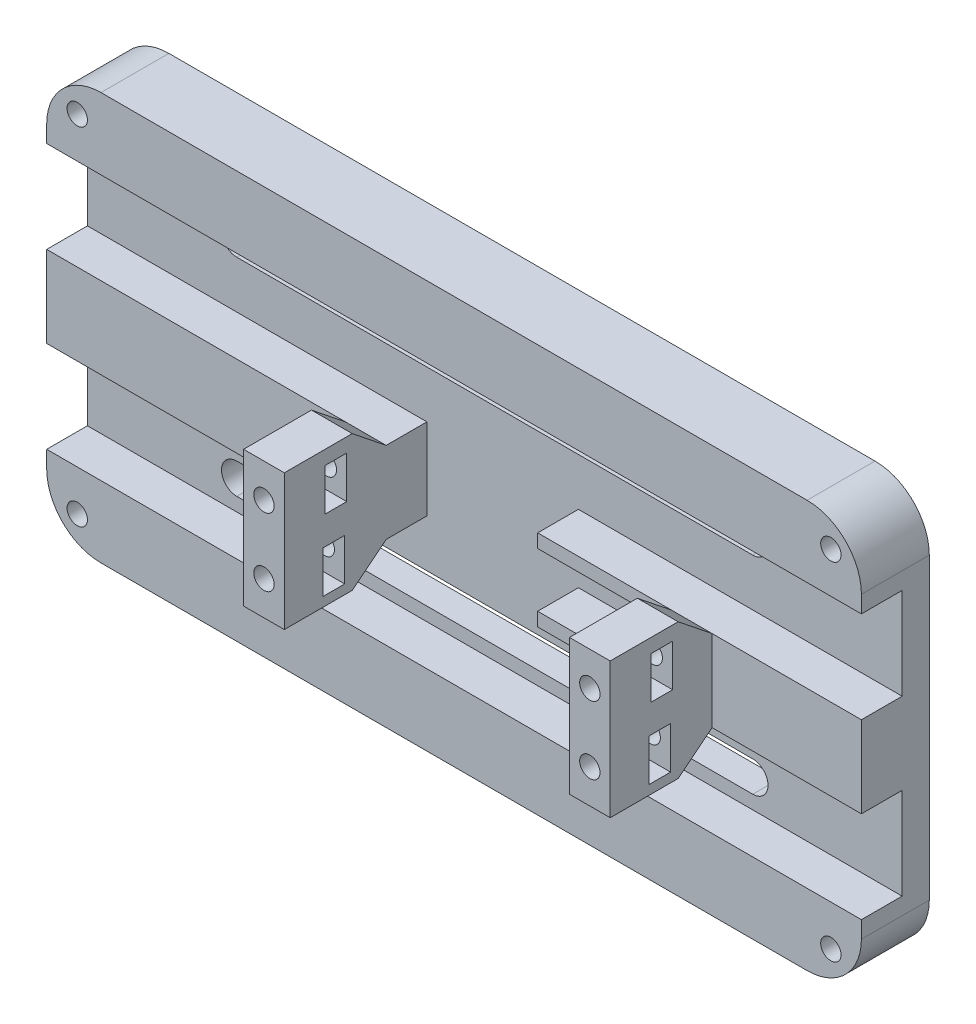
SolidWorks part; units mm, degrees
ref_plane "Front Plane" through (0, 0, 0) normal (0, 0, 1) x (1, 0, 0)
ref_plane "Top Plane" through (0, 0, 0) normal (0, 1, 0) x (1, 0, 0)
ref_plane "Right Plane" through (0, 0, 0) normal (1, 0, 0) x (0, 0, -1)
sketch "Sketch1" plane through (0, 0, 0) normal (0, 0, 1) x (1, 0, 0)
  line L0 (-59.6803, 25.5) -> (60.3197, 25.5)
  line L1 (-59.6803, 36) -> (60.3197, 36)
  line L2 (-59.6803, 36) -> (-59.6803, -24)
  line L3 (-59.6803, -24) -> (60.3197, -24)
  line L4 (60.3197, 36) -> (60.3197, -24)
  line L5 (-59.6803, -13.5) -> (60.3197, -13.5)
  line L6 (-59.6803, 0) -> (-15.6803, 0)
  line L7 (-9.6803, 12) -> (32.3197, 12)
  line L8 (-37.6803, 23.5) -> (38.3197, 23.5)
  line L9 (-37.6803, -11.5) -> (38.3197, -11.5)
  line L10 (-37.6803, 19) -> (38.3197, 19)
  line L11 (-37.6803, -7) -> (38.3197, -7)
  line L17 (38.3197, 12) -> (38.3197, 0)
  line L18 (-9.6803, 0) -> (32.3197, 0)
  line L19 (38.3197, -3.5007) -> (38.3197, 15.5007)
  line L24 (32.3197, 15.5007) -> (32.3197, -3.5007)
  line L26 (38.3197, 12) -> (60.3197, 12)
  line L27 (38.3197, 0) -> (60.3197, 0)
  line L28 (10.3197, 12) -> (10.3197, 10)
  line L29 (10.3197, 10) -> (32.3197, 10)
  line L30 (10.3197, 2) -> (32.3197, 2)
  line L31 (10.3197, 2) -> (10.3197, 0)
  line L32 (32.3197, -4) -> (38.3197, -4)
  line L33 (38.3197, 12) -> (60.3197, 12)
  line L34 (-9.6803, 16) -> (-15.6803, 16)
  line L35 (-9.6803, 16) -> (-9.6803, -4)
  line L36 (-15.6803, 16) -> (-15.6803, -4)
  line L37 (-15.6803, -4) -> (-9.6803, -4)
  line L38 (-59.6803, 12) -> (-15.6803, 12)
  line L39 (32.3197, -3.5007) -> (32.3197, -4)
  line L40 (38.3197, -3.5007) -> (38.3197, -4)
  line L41 (32.3197, 16) -> (38.3197, 16)
  line L42 (32.3197, 16) -> (32.3197, 15.5007)
  line L43 (38.3197, 16) -> (38.3197, 15.5007)
  arc A0 (38.3197, 19) -> (38.3197, 23.5) centre (38.3197, 21.25) ccw
  arc A1 (-37.6803, 23.5) -> (-37.6803, 19) centre (-37.6803, 21.25) ccw
  arc A2 (-37.6803, -7) -> (-37.6803, -11.5) centre (-37.6803, -9.25) ccw
  arc A3 (38.3197, -11.5) -> (38.3197, -7) centre (38.3197, -9.25) ccw
  circle A4 centre (-55.1803, 31.5) radius 1.5
  circle A5 centre (55.8197, 31.5) radius 1.5
  circle A6 centre (-55.1803, -19.5) radius 1.5
  circle A7 centre (55.8197, -19.5) radius 1.5
  circle A8 centre (55.8197, -19.5) radius 3
  circle A9 centre (-55.1803, 31.5) radius 3
  circle A10 centre (-55.1803, -19.5) radius 3
  circle A11 centre (55.8197, 31.5) radius 3
  point P16 (0.3197, 23.5)
  point P19 (0.3197, -11.5)
  point P34 (-37.6803, 6)
  point P37 (38.3197, 6)
  dimension "D1" = 120
  dimension "D4" = 4
  dimension "D2" = 10.5
  dimension "D3" = 10.5
  dimension "D5" = 60
  dimension "D11" = 4.5
  dimension "D12" = 4.5
extrude "Boss-Extrude1" add sketch "Sketch1" along normal blind 10 contours L28 L29 L24 L7 | L30 L31 L18 L24 | L17 L27 L4 L26 | L38 L2 L6 L36 | L5 L2 L3 L4 A10 A8 | L4 L1 L2 L0 A11 A9 region at (0.3197, 30.7148, 0) region at (-37.6803, 6, 0) region at (49.3197, 6, 0) region at (0.3197, -18.7148, 0) region at (21.3197, 11, 0) region at (21.3197, 1, 0)
extrude "Boss-Extrude2" add sketch "Sketch1<5>" along normal blind 25 contours L36 L37 L35 L34 | L24 L19 L17 region at (-12.6803, 6, 0) region at (35.3197, 6, 0)
sketch "Sketch1<5>" plane through (0, 0, 0) normal (0, 0, 1) x (1, 0, 0) same geometry as "Sketch1"
extrude "Boss-Extrude3" add sketch "Sketch1<6>" along normal blind 4 contours L37 L36 L6 L2 L5 L4 L27 L19 L24 L18 L35 A3 L9 A2 L11 | L2 L38 L36 L34 L35 L7 L24 L19 L26 L4 L0 A1 L8 A0 L10 | L7 L35 L18 L31 L30 L24 L29 L28 region at (-0.1152, 18.2008, 0) region at (-0.1152, -6.2008, 0) region at (9.2043, 6, 0)
sketch "Sketch1<6>" plane through (0, 0, 0) normal (0, 0, 1) x (1, 0, 0) same geometry as "Sketch1"
extrude "Boss-Extrude4" add sketch "Sketch1<8>" along normal blind 10 contours A9 A4 | A10 A6 | A8 A7 | A11 region at (52.9046, -19.5, 0) region at (-58.0954, 31.5, 0) region at (-58.0954, -19.5, 0)
sketch "Sketch1<8>" plane through (0, 0, 0) normal (0, 0, 1) x (1, 0, 0) same geometry as "Sketch1"
extrude "Cut-Extrude1" cut sketch "Sketch1<10>" along normal blind 4 contours A11 A5 | A8 A7 | A10 A6 | A9 A4 region at (52.9046, -19.5, 0) region at (-58.0954, 31.5, 0) region at (-58.0954, -19.5, 0) region at (52.9046, 31.5, 0)
sketch "Sketch1<10>" plane through (0, 0, 0) normal (0, 0, 1) x (1, 0, 0) same geometry as "Sketch1"
ref_plane "Plane1" through (-15.6803, 0, 0) normal (-1, 0, 0) x (0, 0, 1)
ref_plane "Plane2" through (0, 0, 25) normal (0, 0, 1) x (1, 0, 0)
sketch "Sketch3" plane through (0, 0, 25) normal (0, 0, 1) x (1, 0, 0)
  line L12 (-15.6803, -4) -> (-9.6803, -4) construction
  line L13 (-9.6803, 16) -> (-15.6803, 16) construction
  circle A0 centre (-12.6803, 11) radius 1.5
  circle A1 centre (-12.6803, 1) radius 1.5
  point P3 (-12.5999, 6)
  dimension "D1" = 5
  dimension "D2" = 10
  dimension "D3" = 5
ref_plane "Plane3" through (0, 0, 25) normal (0, 0, 1) x (1, 0, 0)
sketch "Sketch4" plane through (0, 0, 25) normal (0, 0, 1) x (1, 0, 0)
  circle A0 centre (35.3197, 10.9993) radius 1.5
  circle A1 centre (35.3197, 0.9993) radius 1.5
  point P3 (35.3197, 5.1957)
extrude "Cut-Extrude4" cut sketch "Sketch3" against normal blind 14
extrude "Cut-Extrude5" cut sketch "Sketch4" against normal blind 14
sketch "Sketch5" plane through (-15.6803, 0, 0) normal (-1, 0, 0) x (0, 0, 1)
  line L0 (25, 16) -> (4, 16)
  line L1 (4, 16) -> (4, 12)
  line L2 (4, 12) -> (10, 12)
  line L3 (10, 12) -> (10, 0)
  line L4 (10, 0) -> (4, 0)
  line L5 (4, 0) -> (4, -4)
  line L6 (4, -4) -> (25, -4)
  line L7 (25, -4) -> (25, 16)
  line L8 (15, 16) -> (15, -4)
  line L9 (10, 12) -> (15, 16)
  line L10 (10, 0) -> (15, -4)
  line L11 (19.0092, 13.9313) -> (19.0092, 7.7313)
  line L12 (19.0092, 7.7313) -> (15.8092, 7.7313)
  line L13 (16.107, -2.6244) -> (19.307, -2.6244)
  line L14 (19.0092, 13.9313) -> (15.8092, 13.9313)
  line L15 (15.8092, 13.9313) -> (15.8092, 7.7313)
  line L16 (19.307, 3.5756) -> (16.107, 3.5756)
  line L17 (16.107, 3.5756) -> (16.107, -2.6244)
  line L18 (19.307, -2.6244) -> (19.307, 3.5756)
  dimension "D1" = 6.2
  dimension "D2" = 3.2
  dimension "D3" = 6.2
  dimension "D4" = 3.2
extrude "Cut-Extrude6" cut sketch "Sketch5" against normal blind 59 contours L2 L9 L0 L1 | L10 L4 L5 L6 region at (-15.6803, 14.1961, 8.3725) region at (-15.6803, -2.1961, 8.3725)
extrude "Cut-Extrude8" cut sketch "Sketch5<4>" against normal blind 59 contours L13 L18 L16 L17 | L14 L15 L12 L11 region at (-15.6803, 10.8313, 17.4092) region at (-15.6803, 0.4756, 17.707)
sketch "Sketch5<4>" plane through (-15.6803, 0, 0) normal (-1, 0, 0) x (0, 0, 1) same geometry as "Sketch5"
extrude "Cut-Extrude9" cut sketch "Sketch1<11>" along normal blind 59 contours A5 region at (55.8197, 31.5, 0)
sketch "Sketch1<11>" plane through (0, 0, 0) normal (0, 0, 1) x (1, 0, 0) same geometry as "Sketch1"
ref_plane "Plane4" through (0, 0, 0) normal (0, -1, 0) x (-1, 0, 0)
sketch "Sketch6" plane through (0, 0, 0) normal (0, -1, 0) x (-1, 0, 0)
  line L0 (-12.6361, -4) -> (-10.3197, -4)
  line L1 (-10.3197, -4) -> (-60.3197, -4) construction
  line L2 (-10.3197, -4) -> (-10.3197, -10)
  line L3 (-10.3197, -10) -> (-12.6361, -10)
  line L4 (-10.3197, -10) -> (-32.3197, -10) construction
  line L5 (-12.6361, -10) -> (-12.6361, -4)
extrude "Cut-Extrude10" cut sketch "Sketch6" against normal blind 13
fillet "Fillet1" radius 8 4 edges at (60.3197, 36, 5) (60.3197, -24, 5) (-59.6803, 36, 5) (-59.6803, -24, 5)
ref_plane "Plane5" through (0, 0, 0) normal (0, 0, -1) x (-1, 0, 0)
sketch "Sketch7" plane through (0, 0, 0) normal (0, 0, -1) x (-1, 0, 0)
  circle A0 centre (51.0356, 33.2684) radius 0.85
  circle A1 centre (45.5356, 32.9901) radius 0.85
  circle A3 centre (56.4092, 27.114) radius 0.85
  circle A5 centre (-46.2796, -21.0125) radius 0.85
  circle A6 centre (-51.7796, -21.2907) radius 0.85
  circle A7 centre (-57.1532, -15.1363) radius 0.85
  circle A8 centre (45.5356, 27.114) radius 0.85
  circle A9 centre (-46.2796, -15.1363) radius 0.85
extrude "Cut-Extrude13" cut sketch "Sketch7" against normal blind 6
